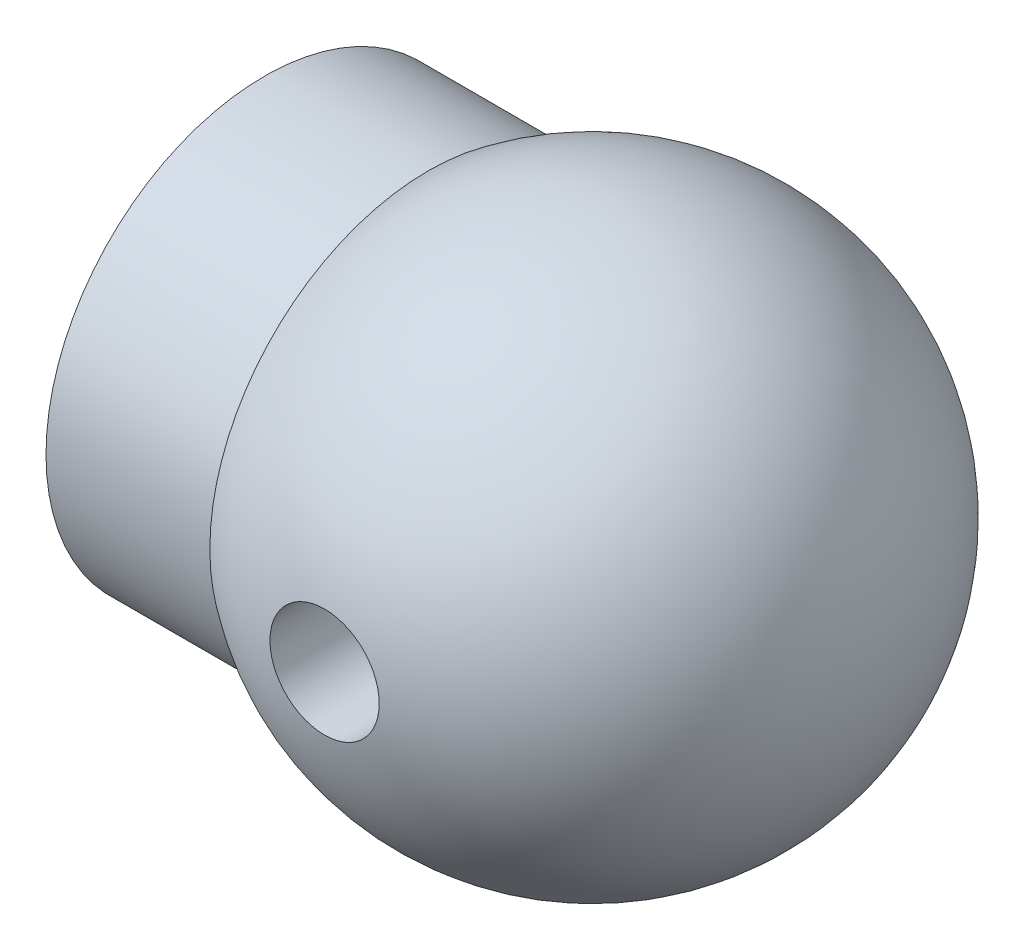
SolidWorks part; units mm, degrees
ref_plane "前视基准面" through (0, 0, 0) normal (0, 0, 1) x (1, 0, 0)
ref_plane "上视基准面" through (0, 0, 0) normal (0, 1, 0) x (1, 0, 0)
ref_plane "右视基准面" through (0, 0, 0) normal (1, 0, 0) x (0, 0, -1)
sketch "草图1" plane through (0, 0, 0) normal (0, 0, 1) x (1, 0, 0)
  line L0 (0, 0) -> (55, 0) construction
  line L1 (0, 0) -> (0, 20)
  line L2 (0, 20) -> (15, 20)
  line L3 (0, 0) -> (55, 0)
  arc A1 (55, 0) -> (15, 20) centre (30, 0) ccw
  dimension "D1" = 20
  dimension "D3" = 25
  dimension "D2" = 15
revolve "旋转1" add sketch "草图1" angle 360 about L0
sketch "草图3" plane through (0, 0, 0) normal (0, 0, 1) x (1, 0, 0)
  circle A0 centre (30, 0) radius 5
  dimension "D1" = 10
extrude "切除-拉伸1" cut sketch "草图3" against normal through all both and the other way through all
